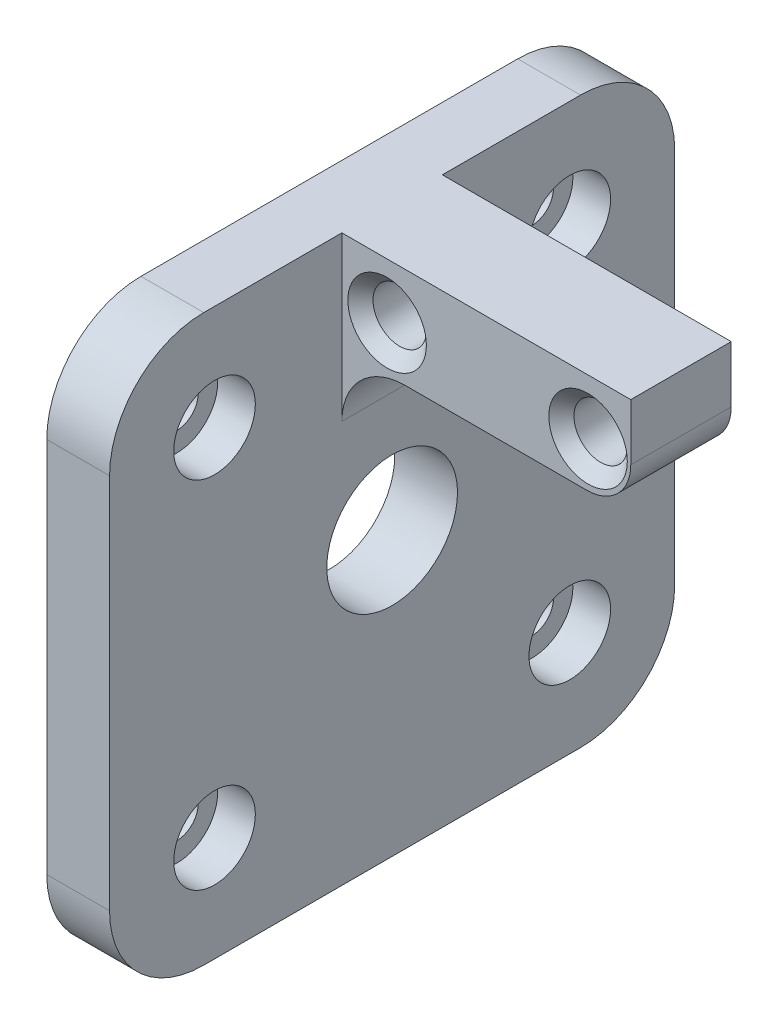
SolidWorks part; units mm, degrees
ref_plane "Front Plane" through (0, 0, 0) normal (0, 0, 1) x (1, 0, 0)
ref_plane "Top Plane" through (0, 0, 0) normal (0, 1, 0) x (1, 0, 0)
ref_plane "Right Plane" through (0, 0, 0) normal (1, 0, 0) x (0, 0, -1)
sketch "Sketch1" plane through (0, 0, 0) normal (1, 0, 0) x (0, 0, -1)
  line L1 (-22.5, -22.5) -> (22.5, -22.5)
  line L2 (-22.5, -22.5) -> (-22.5, 22.5)
  line L3 (-22.5, 22.5) -> (22.5, 22.5)
  line L4 (22.5, -22.5) -> (22.5, 22.5)
  line L5 (-22.5, -22.5) -> (22.5, 22.5) construction
  line L6 (-22.5, 22.5) -> (22.5, -22.5) construction
  line L7 (-4, 22.5) -> (4, 22.5)
  line L8 (-4, 22.5) -> (-4, 14.5)
  line L9 (-4, 14.5) -> (4, 14.5)
  line L10 (4, 22.5) -> (4, 14.5)
  circle A0 centre (0, 0) radius 5.205
  circle A1 centre (0, 0) radius 20 construction
  point P12 (0, 22.5)
  point P13 (0, 0)
  point P14 (2.0207, 4.7275)
  point P15 (0, 14.5)
  point P16 (0, 0)
  point P17 (4, 6.705)
  point P18 (4, 14.0777)
  dimension "D1" = 10.41
  dimension "D4" = 40
  dimension "D2" = 8
  dimension "D3" = 45
  dimension "D5" = 8
extrude "Boss-Extrude1" add sketch "Sketch1" along normal blind 5 contours L3 L10 L9 L8 L2 L1 L4 A0 | L10 L3 L8 L9 region at (0, 0, 21.8636) region at (0, 18.5, 0)
extrude "Boss-Extrude2" add sketch "Sketch1<3>" along normal blind 28 contours L10 L3 L8 L9 region at (0, 18.5, 0)
sketch "Sketch1<3>" plane through (0, 0, 0) normal (1, 0, 0) x (0, 0, -1) same geometry as "Sketch1"
fillet "Fillet1" radius 7.5 4 edges at (2.5, -22.5, 22.5) (2.5, -22.5, -22.5) (2.5, 22.5, -22.5) (2.5, 22.5, 22.5)
fillet "Fillet2" radius 5 1 edges at (5, 14.5, 0)
fillet "Fillet3" radius 3.5 1 edges at (28, 14.5, 0)
sketch "Sketch2" plane through (0, 0, 0) normal (0, 0, 1) x (1, 0, 0)
  circle A0 centre (24.6, 18.1) radius 3.1 construction
  circle A1 centre (8.6, 18.1) radius 3.1
  circle A2 centre (8.6, 18.1) radius 3.1 construction
  circle A3 centre (24.6, 18.1) radius 3.1 construction
  circle A4 centre (8.6, 18.1) radius 2.125
  circle A5 centre (24.6, 18.1) radius 2.125
  dimension "D2" = 4.25
  dimension "D3" = 4.25
  dimension "D1" = 0
extrude "Cut-Extrude1" cut sketch "Sketch2" against normal through all both and the other way through all
hole_wizard "CBORE for M3 SHCS1" positions "Sketch5" profile "Sketch7" counterbore size "M3" standard "ANSI Metric" end condition through all
sketch "Sketch5" plane through (5, 0, 0) normal (1, 0, 0) x (0, 0, -1)
  line L0 (-22.5, 22.5) -> (22.5, -22.5) construction
  line L1 (-22.5, -22.5) -> (22.5, 22.5) construction
  circle A0 centre (0, 0) radius 20 construction
  point P0 (-14.1421, 14.1421)
  point P6 (14.1421, 14.1421)
  point P10 (-14.1421, -14.1421)
  point P12 (14.1421, -14.1421)
sketch "Sketch7" plane through (5, 14.1421, 14.1421) normal (0, 1, 0) x (0, 0, -1)
  line L0 (0, 0) -> (0, 5)
  line L1 (0, 5) -> (1.7, 5)
  line L3 (1.7, 5) -> (1.7, 3)
  line L4 (1.7, 3) -> (3.25, 3)
  line L5 (3.25, 3) -> (3.25, 0)
  line L7 (3.25, 0) -> (0, 0)
  line L11 (0, -6.35) -> (0, 107.95) construction
  dimension "Thru Hole Dia." = 3.4
  dimension "Thru Hole Depth" = 5
  dimension "C'Bore Dia." = 6.5
  dimension "C'Bore Depth" = 3
chamfer "Chamfer1" distance 1 angle 45 2 edges at (24.6, 20.225, 4) (8.6, 20.225, 4)
